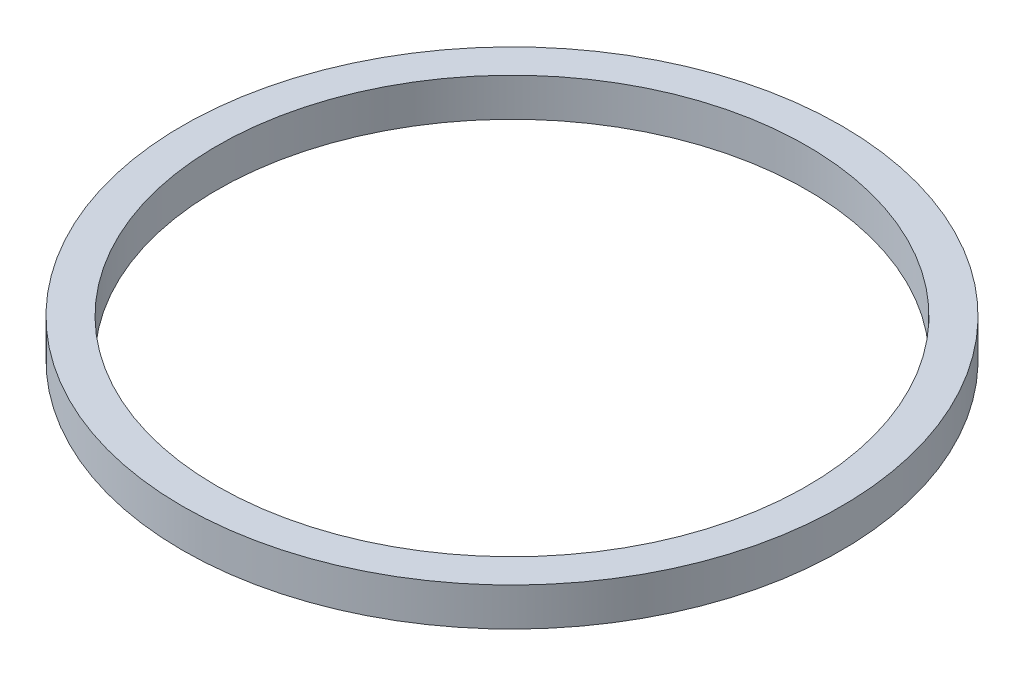
SolidWorks part; units mm, degrees
ref_plane "Front Plane" through (0, 0, 0) normal (0, 0, 1) x (1, 0, 0)
ref_plane "Top Plane" through (0, 0, 0) normal (0, 1, 0) x (1, 0, 0)
ref_plane "Right Plane" through (0, 0, 0) normal (1, 0, 0) x (0, 0, -1)
sketch "Sketch2" plane through (0, 0, 0) normal (0, 1, 0) x (1, 0, 0)
  circle A0 centre (0, 0) radius 8.5
  circle A1 centre (0, 0) radius 9.5
  dimension "D1" = 17
  dimension "D2" = 19
extrude "Boss-Extrude1" add sketch "Sketch2" along normal blind 1.1
